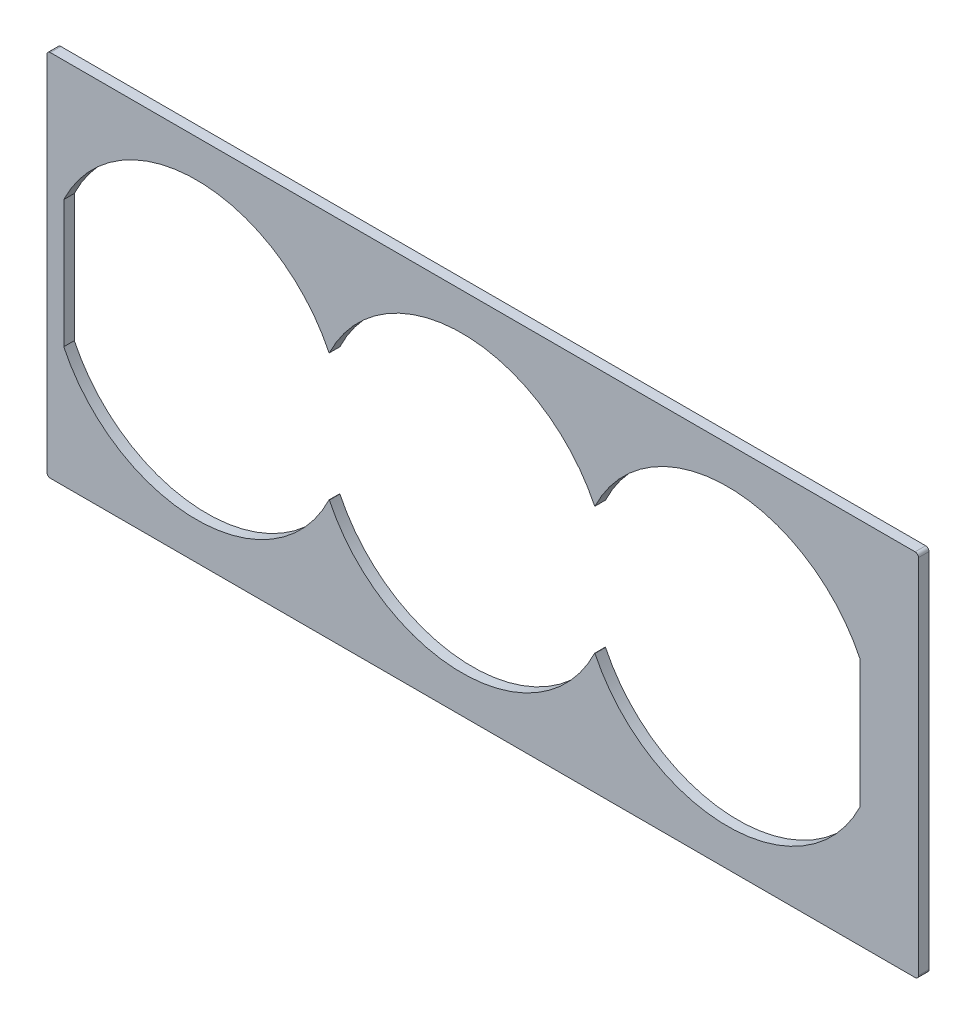
SolidWorks part; units mm, degrees
material "Silicon"
ref_plane "Front" through (0, 0, 0) normal (0, 0, 1) x (1, 0, 0)
ref_plane "Top" through (0, 0, 0) normal (0, 1, 0) x (1, 0, 0)
ref_plane "Right" through (0, 0, 0) normal (1, 0, 0) x (0, 0, -1)
sketch "Sketch4" plane through (0, 0, 0) normal (0, 0, 1) x (1, 0, 0)
  line L0 (165.1, 0) -> (165.1, 139.7) construction
  line L1 (207.493, 93.9963) -> (207.493, 45.7037) construction
  line L2 (0, 0) -> (330.2, 0)
  line L3 (165.1, 69.85) -> (56.604, 69.85) construction
  line L4 (6.35, 93.9963) -> (6.35, 45.7037)
  line L5 (106.858, 93.9963) -> (106.858, 45.7037) construction
  line L6 (0, 0) -> (0, 139.7)
  line L7 (0, 139.7) -> (330.2, 139.7)
  line L8 (330.2, 0) -> (330.2, 139.7)
  line L9 (106.985, 93.9963) -> (106.985, 45.7037) construction
  line L10 (308.128, 93.9963) -> (308.128, 45.7037)
  line L11 (207.62, 93.9963) -> (207.62, 45.7037) construction
  line L12 (106.858, 93.9963) -> (106.985, 93.9963)
  line L13 (207.493, 93.9963) -> (207.62, 93.9963)
  line L14 (207.62, 45.7037) -> (207.493, 45.7037)
  line L15 (106.985, 45.7037) -> (106.858, 45.7037)
  arc A0 (6.35, 45.7037) -> (106.858, 45.7037) centre (56.604, 69.85) ccw
  arc A1 (106.858, 93.9963) -> (6.35, 93.9963) centre (56.604, 69.85) ccw
  arc A2 (106.985, 45.7037) -> (207.493, 45.7037) centre (157.239, 69.85) ccw
  arc A3 (207.493, 93.9963) -> (106.985, 93.9963) centre (157.239, 69.85) ccw
  arc A4 (207.62, 45.7037) -> (308.128, 45.7037) centre (257.874, 69.85) ccw
  arc A5 (308.128, 93.9963) -> (207.62, 93.9963) centre (257.874, 69.85) ccw
  point P8 (165.1, 69.85)
  dimension "D2" = 111.508
  dimension "D1" = 100.508
  dimension "D3" = 139.7
  dimension "D4" = 330.2
  dimension "D6" = 6.35
  dimension "D7" = 0.127
  dimension "D5" = 3
extrude "DIMENSIONS CONTROL OPTICS LOCATION" add sketch "Sketch4" along normal blind 4
fillet "Fillet1" radius 1.27 4 edges at (330.2, 139.7, 2) (0, 0, 2) (0, 139.7, 2) (330.2, 0, 2)
